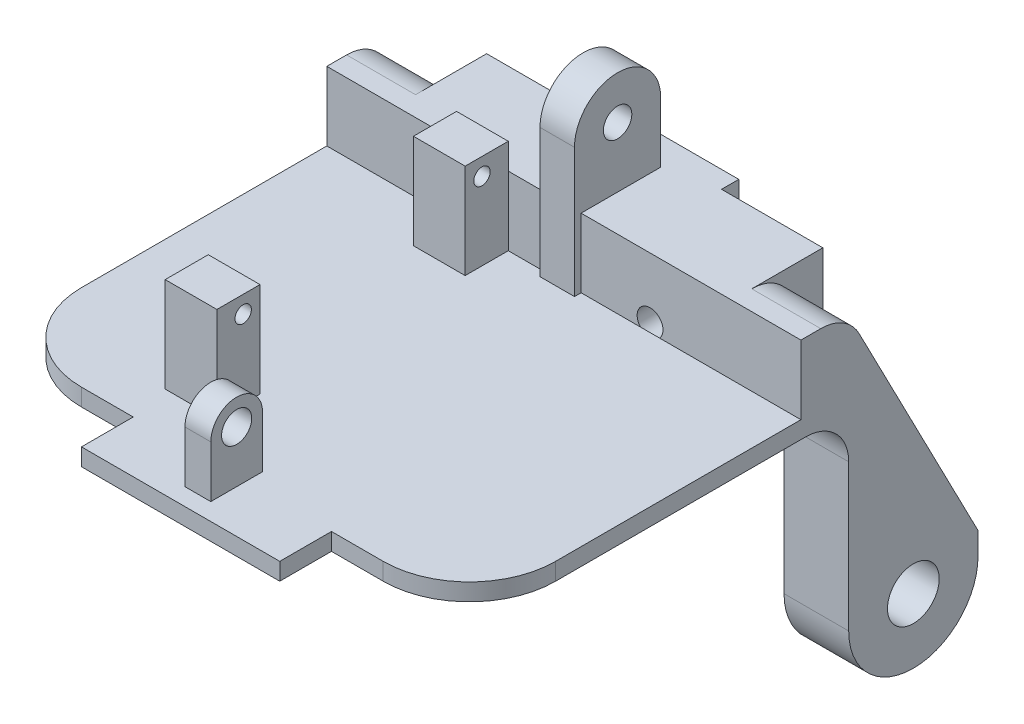
SolidWorks part; units mm, degrees
ref_plane "前视基准面" through (0, 0, 0) normal (0, 0, 1) x (1, 0, 0)
ref_plane "上视基准面" through (0, 0, 0) normal (0, 1, 0) x (1, 0, 0)
ref_plane "右视基准面" through (0, 0, 0) normal (1, 0, 0) x (0, 0, -1)
sketch "草图1" plane through (0, 0, 0) normal (0, 1, 0) x (1, 0, 0)
  line L1 (-27.5, -19.5) -> (27.5, -19.5)
  line L2 (-27.5, -19.5) -> (-27.5, 19.5)
  line L3 (-27.5, 19.5) -> (27.5, 19.5)
  line L4 (27.5, -19.5) -> (27.5, 19.5)
  line L5 (-27.5, -19.5) -> (27.5, 19.5) construction
  line L6 (-27.5, 19.5) -> (27.5, -19.5) construction
  point P0 (0, 0)
  dimension "D1" = 55
  dimension "D2" = 39
extrude "凸台-拉伸1" add sketch "草图1" along normal blind 2
sketch "草图2" plane through (0, 2, 0) normal (0, 1, 0) x (1, 0, 0)
  line L0 (-27.5, -19.5) -> (27.5, -19.5) construction
  line L1 (-11.5, -19.5) -> (11.5, -19.5)
  line L2 (-11.5, -19.5) -> (-11.5, -25.5)
  line L3 (-11.5, -25.5) -> (11.5, -25.5)
  line L4 (11.5, -19.5) -> (11.5, -25.5)
  line L5 (27.5, 19.5) -> (-27.5, 19.5) construction
  point P9 (0, -25.5)
  dimension "D1" = 23
  dimension "D2" = 45
extrude "凸台-拉伸2" add sketch "草图2" against normal blind 2
sketch "草图3" plane through (0, 2, 0) normal (0, 1, 0) x (1, 0, 0)
  line L1 (-6.45, -14.8415) -> (-12.45, -14.8415)
  line L2 (-6.45, -14.8415) -> (-6.45, -9.8415)
  line L3 (-6.45, -9.8415) -> (-12.45, -9.8415)
  line L4 (-12.45, -14.8415) -> (-12.45, -9.8415)
  line L6 (-6.45, 13.9585) -> (-12.45, 13.9585)
  line L7 (-6.45, 13.9585) -> (-6.45, 18.9585)
  line L8 (-6.45, 18.9585) -> (-12.45, 18.9585)
  line L9 (-12.45, 13.9585) -> (-12.45, 18.9585)
  dimension "D1" = 6.45
  dimension "D2" = 23.8
  dimension "D3" = 6.45
  dimension "D4" = 6
  dimension "D5" = 6
  dimension "D6" = 5
  dimension "D7" = 5
extrude "凸台-拉伸3" add sketch "草图3" along normal blind 11
sketch "草图5" plane through (-12.45, 0, 0) normal (-1, 0, 0) x (0, 0, 1)
  line L0 (-13.9585, 13) -> (-13.9585, 2) construction
  line L1 (9.8415, 13) -> (9.8415, 2) construction
  line L2 (-19.5, 2) -> (19.5, 2) construction
  line L3 (9.8415, 2) -> (14.8415, 2) construction
  circle A0 centre (-15.9085, 11) radius 0.95
  circle A1 centre (11.7915, 11) radius 0.95
  dimension "D1" = 1.95
  dimension "D2" = 1.95
  dimension "D3" = 9
  dimension "D4" = 9
  dimension "D5" = 27.7
  dimension "D6" = 1.9
  dimension "D7" = 1.9
extrude "切除-拉伸1" cut sketch "草图5" against normal blind 11
sketch "草图6" plane through (0, 2, 0) normal (0, 1, 0) x (1, 0, 0)
  line L0 (27.5, -19.5) -> (27.5, 19.5) construction
  line L1 (-27.5, 19.5) -> (27.5, 19.5)
  line L2 (-27.5, 19.5) -> (-27.5, 18.9585)
  line L3 (-27.5, 18.9585) -> (27.5, 18.9585)
  line L4 (27.5, 19.5) -> (27.5, 18.9585)
  line L5 (-6.45, 18.9585) -> (-12.45, 18.9585) construction
extrude "凸台-拉伸4" add sketch "草图6" along normal blind 8
sketch "草图8" plane through (0, 0, 0) normal (1, 0, 0) x (0, 0, -1)
  line L0 (28.1899, 17) -> (28.1899, 0)
  line L1 (-19.5, 2) -> (18.9585, 2) construction
  line L2 (18.1899, 17) -> (18.1899, 0)
  line L4 (18.1899, 0) -> (28.1899, 0)
  line L7 (-19.5, 0) -> (19.5, 0) construction
  arc A0 (28.1899, 17) -> (18.1899, 17) centre (23.1899, 17) ccw
  circle A1 centre (23.1899, 17) radius 1.65
  dimension "D1" = 15
  dimension "D2" = 10
  dimension "D3" = 3.3
extrude "凸台-拉伸6" add sketch "草图8" along normal mid plane 4
sketch "草图10" plane through (0, 2, 0) normal (0, 1, 0) x (1, 0, 0)
  line L0 (-11.5, -25.5) -> (11.5, -25.5) construction
  line L1 (-1.5, -17.5) -> (1.5, -17.5)
  line L2 (-1.5, -17.5) -> (-1.5, -23.5)
  line L3 (-1.5, -23.5) -> (1.5, -23.5)
  line L4 (1.5, -17.5) -> (1.5, -23.5)
  point P7 (0, -17.5)
  dimension "D1" = 2
  dimension "D2" = 3
  dimension "D3" = 6
extrude "凸台-拉伸7" add sketch "草图10" along normal blind 9
sketch "草图11" plane through (0, 0, -18.9585) normal (0, 0, 1) x (1, 0, 0)
  line L0 (-2, 10) -> (-27.5, 10) construction
  circle A0 centre (-10, 3) radius 1.5
  dimension "D1" = 10
  dimension "D2" = 3
  dimension "D3" = 7
extrude "切除-拉伸3" cut sketch "草图11" against normal blind 13
sketch "草图12" plane through (-27.5, 0, 0) normal (-1, 0, 0) x (0, 0, 1)
  line L1 (-19.5, 0) -> (4.0888, 0)
  line L2 (-19.5, 0) -> (19.5, 0) construction
  line L3 (-19.5, 10) -> (-19.5, 0) construction
  line L4 (-39.5, -22) -> (-39.5, 10)
  line L5 (-19.5, 10) -> (-39.5, 10)
  line L6 (-24.5, -22) -> (-24.5, 0)
  line L7 (-24.5, 0) -> (-19.5, 0)
  line L8 (-19.5, 10) -> (-19.5, 0)
  arc A0 (-39.5, -22) -> (-24.5, -22) centre (-32, -22) ccw
  circle A2 centre (-32, -22) radius 3
  line M7 (-19.5, 10) -> (-19.5, 0)
  dimension "D1" = 15
  dimension "D5" = 6
  dimension "D2" = 22
  dimension "D3" = 12.5
extrude "凸台-拉伸8" add sketch "草图12" against normal blind 7.5 contours L4 A0 L6 L7 L5 A2 M7 region at (-27.5, -7.1737, -31.1527)
sketch "草图13" plane through (0, 0, 0) normal (0, -1, 0) x (1, 0, 0)
  line L0 (-11.5, 25.5) -> (11.5, 25.5) construction
  line L1 (-5, 21) -> (5, 21)
  line L2 (-5, 21) -> (-5, 17.3)
  line L3 (-5, 17.3) -> (5, 17.3)
  line L4 (5, 21) -> (5, 17.3)
  line L5 (-5, 21) -> (5, 17.3) construction
  line L6 (-5, 17.3) -> (5, 21) construction
  point P0 (0, 19.15)
  dimension "D1" = 10
  dimension "D2" = 4.5
  dimension "D3" = 3.7
extrude "凸台-拉伸9" add sketch "草图13" along normal blind 1
mirror "镜向1" about plane through (0, 0, 0) normal (1, 0, 0) of "凸台-拉伸8", "切除-拉伸3"
fillet "圆角3" 2 edges at (0, 11, 17.5) (0, 11, 23.5) type full round first side face at (0, 6.5, 17.5) second side face at (0, 6.5, 23.5) middle face at (0, 11, 20.5)
sketch "草图15" plane through (-1.5, 0, 0) normal (-1, 0, 0) x (0, 0, 1)
  circle A0 centre (20.5, 8) radius 1.75
  dimension "D1" = 3.5
extrude "切除-拉伸5" cut sketch "草图15" against normal blind 23
sketch "草图16" plane through (0, 0, -19.5) normal (0, 0, -1) x (-1, 0, 0)
  line L0 (-20, 10) -> (-2, 10) construction
  line L1 (-7.75, 10) -> (7.75, 10)
  line L2 (-7.75, 10) -> (-7.75, 6)
  line L3 (-7.75, 6) -> (7.75, 6)
  line L4 (7.75, 10) -> (7.75, 6)
  point P6 (0, 6)
  dimension "D1" = 15.5
  dimension "D2" = 4
extrude "凸台-拉伸10" add sketch "草图16" along normal blind 20
sketch "草图17" plane through (0, 0, -19.5) normal (0, 0, -1) x (-1, 0, 0)
  line L6 (-20, 0) -> (-2, 0)
  line L7 (-20, 0) -> (-2, 0)
  line L8 (-20, 10) -> (-20, 0)
  line L10 (-7.75, 6) -> (-7.75, 10)
  line L11 (-7.75, 10) -> (-20, 10)
  line L12 (-2, 0) -> (-2, 6)
  line L14 (-2, 0) -> (-2, 6)
  line L15 (-7.75, 6) -> (-7.75, 10)
  line L16 (-2, 6) -> (-7.75, 6)
  line L18 (-2, 6) -> (-7.75, 6)
  line L21 (-7.75, 10) -> (-20, 10)
  line L32 (-20, 10) -> (-20, 0)
  line L33 (7.75, 6) -> (2, 6)
  line L34 (2, 6) -> (2, 0)
  line L35 (2, 0) -> (20, 0)
  line L36 (20, 0) -> (20, 10)
  line L37 (20, 10) -> (7.75, 10)
  line L38 (7.75, 10) -> (7.75, 6)
  line L39 (7.75, 6) -> (2, 6)
  line L40 (2, 6) -> (2, 0)
  line L41 (2, 0) -> (20, 0)
  line L42 (20, 0) -> (20, 10)
  line L43 (20, 10) -> (7.75, 10)
  line L44 (7.75, 10) -> (7.75, 6)
  circle A0 centre (10, 3) radius 1.5 construction
  circle A1 centre (-10, 3) radius 1.5 construction
  circle A2 centre (10, 3) radius 1.5
  circle A3 centre (-10, 3) radius 1.5
  dimension "D1" = 0
  dimension "D2" = 0
extrude "凸台-拉伸11" add sketch "草图17" along normal blind 10
fillet "圆角4" radius 10 2 edges at (23.75, 10, -39.5) (-23.75, 10, -39.5)
sketch "草图18" plane through (0, 10, 0) normal (0, 1, 0) x (1, 0, 0)
  line L0 (-7.75, 39.5) -> (7.75, 39.5) construction
  line L1 (-14.1233, 41.9545) -> (12.4415, 41.9545)
  line L2 (-14.1233, 41.9545) -> (-14.1233, 31.5)
  line L3 (-14.1233, 31.5) -> (12.4415, 31.5)
  line L4 (12.4415, 41.9545) -> (12.4415, 31.5)
  dimension "D1" = 8
extrude "切除-拉伸6" cut sketch "草图18" against normal blind 10
sketch "草图19" plane through (27.5, 0, 0) normal (1, 0, 0) x (0, 0, -1)
  line L0 (24.3, 10) -> (39.5, -19.3956)
  line L1 (39.5, -22) -> (39.5, 0) construction
  line L2 (24.3, 10) -> (39.5, 10)
  line L3 (39.5, 10) -> (39.5, -19.3956)
  dimension "D1" = 15.2
extrude "切除-拉伸7" cut sketch "草图19" against normal blind 8
sketch "草图20" plane through (-27.5, 0, 0) normal (-1, 0, 0) x (0, 0, 1)
  line L0 (-24.3, 10) -> (-39.5, 10)
  line L1 (-39.5, 10) -> (-39.5, -19.3956)
  line L8 (-39.5, -19.3956) -> (-39.5, -22)
  line L9 (-24.3, 10) -> (-39.5, -19.3956)
  line L10 (-18.9585, 10) -> (-24.3, 10)
  line L11 (-18.9585, 2) -> (-18.9585, 10)
  line L12 (19.5, 2) -> (-18.9585, 2)
  line L13 (19.5, 0) -> (19.5, 2)
  line L14 (-24.5, 0) -> (19.5, 0)
  line L15 (-24.5, -22) -> (-24.5, 0)
  line L17 (-24.3, 10) -> (-39.5, -19.3956)
  arc A1 (-39.5, -22) -> (-24.5, -22) centre (-32, -22) ccw
  dimension "D1" = 0
extrude "切除-拉伸8" cut sketch "草图20" against normal blind 8
fillet "圆角6" radius 5 4 edges at (23.75, 0, -24.5) (-23.75, 0, -24.5) (23.5, 10, -24.3) (-23.5, 10, -24.3)
sketch "草图21" plane through (0, -1, 0) normal (0, -1, 0) x (1, 0, 0)
  line L0 (-5, 17.3) -> (5, 17.3) construction
  circle A0 centre (0, 19) radius 1.4
  dimension "D1" = 2.8
  dimension "D2" = 1.7
  dimension "D3" = 27.5
extrude "切除-拉伸9" cut sketch "草图21" against normal blind 4
fillet "圆角7" radius 10 2 edges at (-27.5, 1, 19.5) (27.5, 1, 19.5)
